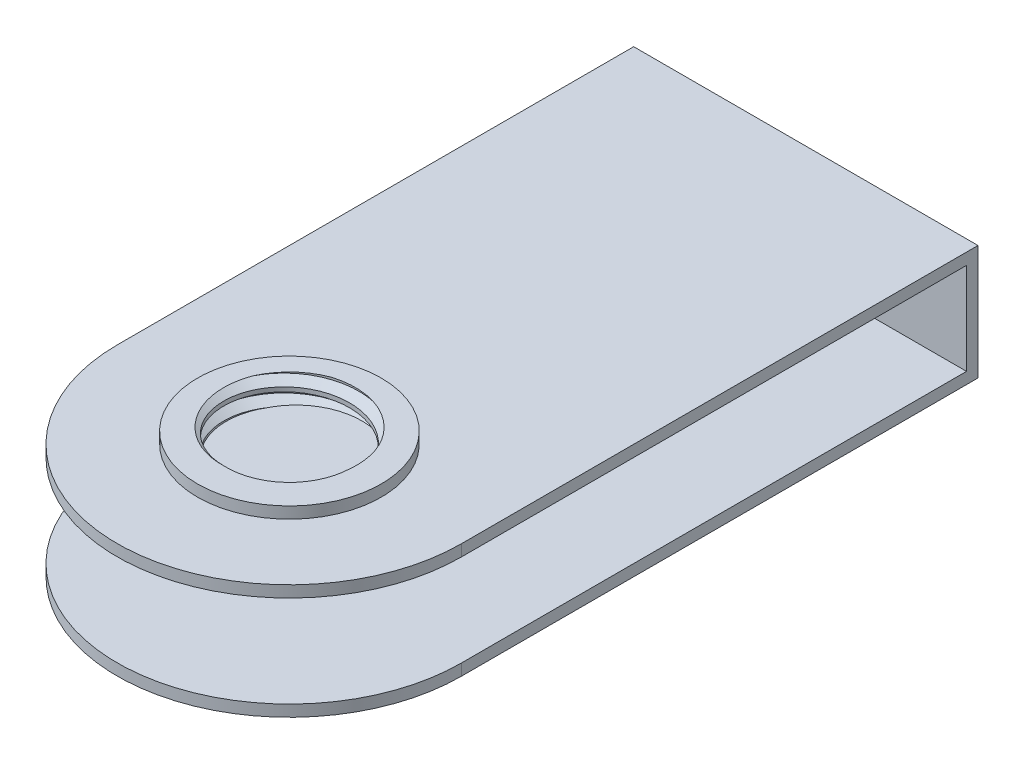
SolidWorks part; units mm, degrees
ref_plane "Ebene vorne" through (0, 0, 0) normal (0, 0, 1) x (1, 0, 0)
ref_plane "Ebene oben" through (0, 0, 0) normal (0, 1, 0) x (1, 0, 0)
ref_plane "Ebene rechts" through (0, 0, 0) normal (1, 0, 0) x (0, 0, -1)
sketch "Skizze1" plane through (0, 0, 0) normal (0, 1, 0) x (1, 0, 0)
  line L1 (15, -22.5) -> (-15, -22.5)
  line L2 (15, -22.5) -> (15, 22.5)
  line L3 (15, 22.5) -> (-15, 22.5)
  line L4 (-15, -22.5) -> (-15, 22.5)
  line L5 (15, -22.5) -> (-15, 22.5) construction
  line L6 (15, 22.5) -> (-15, -22.5) construction
  arc A0 (15, -22.5) -> (-15, -22.5) centre (0, -22.5) cw
  point P0 (0, 0)
  dimension "D1" = 30
  dimension "D2" = 45
extrude "Aufsatz-Linear austragen1" add sketch "Skizze1" along normal blind 1 contours A0 L1 | L4 L1 L2 L3 region at (0, 0, 28.8662) region at (0, 0, 0)
sketch "Skizze2" plane through (0, 0, 0) normal (0, -1, 0) x (1, 0, 0)
  line L0 (15, 22.5) -> (15, -22.5) construction
  line L1 (-15, -22.5) -> (15, -22.5)
  line L2 (-15, -22.5) -> (-15, -21.5)
  line L3 (-15, -21.5) -> (15, -21.5)
  line L4 (15, -22.5) -> (15, -21.5)
  dimension "D1" = 1
extrude "Aufsatz-Linear austragen2" add sketch "Skizze2" along normal blind 8
ref_plane "Ebene1" through (0, -8, 0) normal (0, -1, 0) x (-1, 0, 0)
sketch "Skizze3" plane through (0, -8, 0) normal (0, -1, 0) x (-1, 0, 0)
  line L1 (15, 22.5) -> (-15, 22.5)
  line L2 (15, 22.5) -> (15, -22.5)
  line L3 (15, -22.5) -> (-15, -22.5)
  line L4 (-15, 22.5) -> (-15, -22.5)
  arc A0 (15, -22.5) -> (-15, -22.5) centre (0, -22.5) cw
  arc A1 (-15, -22.5) -> (15, -22.5) centre (0, -22.5) ccw construction
extrude "Aufsatz-Linear austragen3" add sketch "Skizze3" along normal blind 1 contours L1 L4 L3 L2 | A0 L3 | L2 L1 L4 L3 region at (0, -8, 0) region at (0, -8, 28.8662)
sketch "Skizze12" plane through (0, 1, 0) normal (0, 1, 0) x (1, 0, 0)
  circle A0 centre (0, -22.5) radius 8
extrude "Aufsatz-Linear austragen5" add sketch "Skizze12" along normal blind 1
sketch "Skizze13" plane through (0, 2, 0) normal (0, 1, 0) x (1, 0, 0)
  circle A0 centre (0, -22.5) radius 6.3
extrude "Schnitt-Linear austragen3" cut sketch "Skizze13" against normal blind 2
thread "Gewinde2" pitch 1.5 method extrude profile "Gewindeprofil3" start angle 0, offset 1.6, length 4, pitch 1.5, diameter 12.6
ref_plane "Ebene4" through (-6.3, 3.6, 22.5) normal (0, 0, 1) x (-1, 0, 0)
sketch "Gewindeprofil3" plane through (-6.3, 3.6, 22.5) normal (0, 0, 1) x (-1, 0, 0)
  line L0 (0, 0) -> (0, 1.5) construction
  line L11 (0, 0) -> (0, 1.3125)
  line L12 (0, 1.3125) -> (-0.8119, 0.8437)
  line L13 (-0.8119, 0.8437) -> (-0.8119, 0.4687)
  line L15 (-0.8119, 0.4687) -> (0, 0)
  line L17 (-0.8119, 0.6562) -> (0, 0.6562) construction
  point P2 (0, 0)
  dimension "Pitch" = 1.5
  dimension "Profile_Angle" = 60
  dimension "Profile_Land" = 0.375
  dimension "Profile_Height" = 0.8119
sketch "Skizze16" plane through (0, 2, 0) normal (0, 1, 0) x (1, 0, 0)
  circle A0 centre (0, -22.5) radius 8
extrude "Schnitt-Linear austragen4" cut sketch "Skizze16" along normal blind 5
sketch "Skizze17" plane through (0, 0, 0) normal (0, -1, 0) x (1, 0, 0)
  circle A0 centre (0, 22.5) radius 10.9844
extrude "Schnitt-Linear austragen5" cut sketch "Skizze17" along normal blind 5
sketch "Skizze20" plane through (0, -9, 0) normal (0, -1, 0) x (-1, 0, 0)
  text T0 "\r\n\r\n\r\n\r\n              EAH Jena" font "Arial" height 3.5
extrude "Aufsatz-Linear austragen6" add sketch "Skizze20" along normal blind 1
sketch "Skizze21" plane through (0, -9, 0) normal (0, -1, 0) x (1, 0, 0)
  line L0 (11.2939, -17.5001) -> (11.2939, -14.0001)
  line L1 (11.2939, -14.0001) -> (8.2613, -15.7527)
  line L2 (8.2613, -15.7527) -> (11.2939, -17.5001)
  line L30 (11.2573, -13.0001) -> (11.2573, -9.5001)
  line L31 (11.2573, -9.5001) -> (8.2247, -11.2527)
  line L32 (8.2247, -11.2527) -> (11.2573, -13.0001)
  line L35 (11.2755, -8.5003) -> (11.2755, -5.0003)
  line L36 (11.2755, -5.0003) -> (8.2429, -6.7529)
  line L37 (8.2429, -6.7529) -> (11.2755, -8.5003)
  line L38 (7.6446, -15.1401) -> (7.6446, -11.6401)
  line L39 (7.6446, -11.6401) -> (4.612, -13.3927)
  line L40 (4.612, -13.3927) -> (7.6446, -15.1401)
  line L41 (7.6542, -10.6699) -> (7.6542, -7.1699)
  line L42 (7.6542, -7.1699) -> (4.6217, -8.9225)
  line L43 (4.6217, -8.9225) -> (7.6542, -10.6699)
  line L44 (3.9966, -12.836) -> (3.9966, -9.336)
  line L45 (3.9966, -9.336) -> (0.964, -11.0886)
  line L46 (0.964, -11.0886) -> (3.9966, -12.836)
  line L47 (8.1269, -10.7034) -> (8.1269, -7.2034)
  line L50 (11.1595, -8.956) -> (8.1269, -10.7034)
  line L51 (8.1269, -7.2034) -> (11.1595, -8.956)
  line L52 (8.1742, -15.2279) -> (8.1742, -11.7279)
  line L53 (11.2067, -13.4804) -> (8.1742, -15.2279)
  line L54 (8.1742, -11.7279) -> (11.2067, -13.4804)
  line L55 (4.4895, -12.8876) -> (4.4895, -9.3876)
  line L56 (7.5221, -11.1402) -> (4.4895, -12.8876)
  line L57 (4.4895, -9.3876) -> (7.5221, -11.1402)
  dimension "D1" = 3.5
  dimension "D2" = 3.5
  dimension "D3" = 1
  dimension "D5" = 1
extrude "Aufsatz-Linear austragen7" add sketch "Skizze21" along normal blind 1 contours L39 L40 L38 | L45 L46 L44 | L57 L55 L56 | L42 L43 L41 | L54 L52 L53 | L31 L32 L30 | L51 L47 L50 | L36 L37 L35 | L1 L2 region at (10.283, -9, -15.751) region at (10.2465, -9, -11.251) region at (10.2646, -9, -6.7512) region at (6.6338, -9, -13.391) region at (6.6434, -9, -8.9208) region at (2.9857, -9, -11.0869) region at (9.1377, -9, -8.9543) region at (9.185, -9, -13.4787) region at (5.5004, -9, -11.1385)
